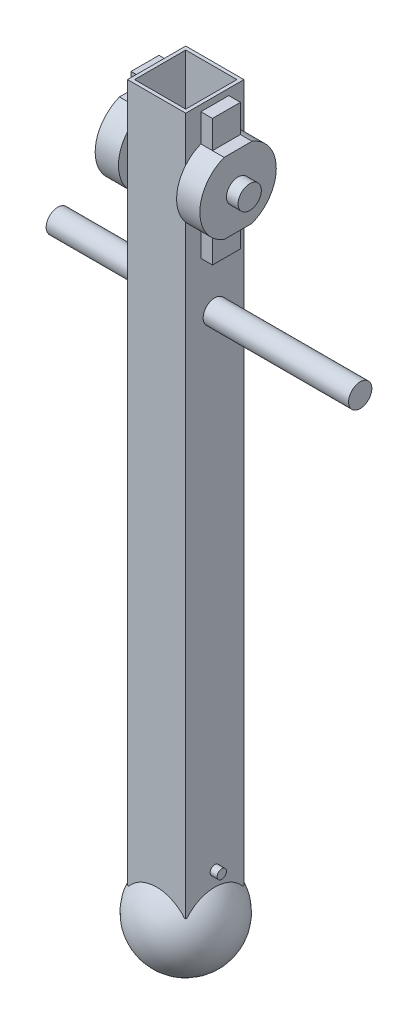
SolidWorks part; units mm, degrees
ref_plane "Front Plane" through (0, 0, 0) normal (0, 0, 1) x (1, 0, 0)
ref_plane "Top Plane" through (0, 0, 0) normal (0, 1, 0) x (1, 0, 0)
ref_plane "Right Plane" through (0, 0, 0) normal (1, 0, 0) x (0, 0, -1)
sketch "Sketch1" plane through (0, 0, 0) normal (0, 1, 0) x (1, 0, 0)
  line L0 (0, 56.0843) -> (0, -54.0393) construction
  line L1 (-85.0637, 0) -> (105.2276, 0) construction
  line L3 (-12.5, 12.5) -> (12.5, 12.5)
  line L4 (-12.5, 12.5) -> (-12.5, -12.5)
  line L5 (-12.5, -12.5) -> (12.5, -12.5)
  line L6 (12.5, 12.5) -> (12.5, -12.5)
  line L7 (-12.5, 12.5) -> (12.5, -12.5) construction
  line L8 (-12.5, -12.5) -> (12.5, 12.5) construction
  point P5 (0, 0)
  dimension "D1" = 25
  dimension "D2" = 25
extrude "Boss-Extrude1" add sketch "Sketch1" along normal blind 300
sketch "Sketch3" plane through (0, 0, 0) normal (0, -1, 0) x (1, 0, 0)
  line L0 (0, 13.6526) -> (0, -14.5281) construction
  line L1 (-18.6047, 0) -> (18.7142, 0) construction
  line L4 (-11, 11) -> (11, 11)
  line L5 (-11, 11) -> (-11, -11)
  line L6 (-11, -11) -> (11, -11)
  line L7 (11, 11) -> (11, -11)
  line L8 (-11, 11) -> (11, -11) construction
  line L9 (-11, -11) -> (11, 11) construction
  point P5 (0, 0)
  dimension "D1" = 22
  dimension "D2" = 22
extrude "Cut-Extrude1" cut sketch "Sketch3" against normal blind 300
ref_plane "Plane1" through (0, -10, 0) normal (0, -1, 0) x (-1, 0, 0)
sketch "Sketch4" plane through (0, -10, 0) normal (0, -1, 0) x (-1, 0, 0)
  line L0 (0, 13.2121) -> (0, -13.9344) construction
  line L1 (0, 20) -> (0, -20)
  arc A0 (0, 20) -> (0, -20) centre (0, 0) ccw
  dimension "D2" = 20
  dimension "D1" = 40
revolve "Revolve1" add sketch "Sketch4" angle 360 about L0
sketch "Sketch6" plane through (12.5, 0, 0) normal (1, 0, 0) x (0, 0, -1)
  line L0 (0, 22.0983) -> (0, -32.6766) construction
  line L1 (41.5847, -10) -> (-39.8607, -10) construction
  line L2 (-0.2807, -10) -> (0.2807, -10) construction
  circle A0 centre (0, 12) radius 2
  dimension "D2" = 4
  dimension "D1" = 22
extrude "Cut-Extrude3" cut sketch "Sketch6" against normal blind 25
sketch "Sketch9" plane through (-12.5, 0, 0) normal (-1, 0, 0) x (0, 0, 1)
  circle A0 centre (0, 12) radius 1.99
extrude "Boss-Extrude8" add sketch "Sketch9" against normal blind 28 separate body
sketch "Sketch10" plane through (-12.5, 0, 0) normal (-1, 0, 0) x (0, 0, 1)
  circle A0 centre (0, 12) radius 1.99
extrude "Boss-Extrude9" add sketch "Sketch10" along normal blind 3
sketch "Sketch11" plane through (12.5, 0, 0) normal (1, 0, 0) x (0, 0, -1)
  line L0 (0, 385.4895) -> (0, -90.331) construction
  line L1 (-12.5, 300) -> (12.5, 300) construction
  line L5 (-6, 285.2889) -> (-6, 297.2889)
  line L6 (6, 254.7111) -> (6, 242.7111)
  line L7 (6, 242.7111) -> (-6, 242.7111)
  line L8 (-6, 242.7111) -> (-6, 254.7111)
  line L9 (6, 285.2889) -> (6, 297.2889)
  line L10 (6, 297.2889) -> (-6, 297.2889)
  circle A1 centre (0, 270) radius 5
  circle A2 centre (0, 270) radius 16.4241
  arc A5 (-6, 254.7111) -> (6, 254.7111) centre (0, 270) ccw
  arc A6 (-6, 285.2889) -> (6, 285.2889) centre (0, 270) cw
  dimension "D1" = 12
  dimension "D2" = 30
  dimension "D3" = 6
  dimension "D8" = 12
  dimension "D4" = 6
  dimension "D5" = 6
  dimension "D6" = 6
  dimension "D7" = 12
extrude "Boss-Extrude10" add sketch "Sketch11" along normal blind 10 separate body contours A5 L0 L7 L6 | A1 L0 | L0 A1 | L0 A2 L8 L7 | A2 | L5 L10 L9 A6 region at (12.5, 270, -2.1221) region at (12.5, 270, 2.1221) region at (12.5, 248.3351, 3.0501) region at (12.5, 248.3351, -3.0501)
sketch "Sketch12" plane through (12.5, 0, 0) normal (1, 0, 0) x (0, 0, -1)
  line L3 (-12.5, 300) -> (12.5, 300) construction
  circle A5 centre (0, 270) radius 5
  circle A6 centre (0, 220) radius 5
  point P8 (0, 0)
  dimension "D1" = 80
extrude "Cut-Extrude4" cut sketch "Sketch12" against normal blind 1.5
sketch "Sketch15" plane through (22.5, 0, 0) normal (1, 0, 0) x (0, 0, -1)
  line L0 (-6, 254.7111) -> (-6, 242.7111)
  line L1 (-6, 242.7111) -> (6, 242.7111)
  line L2 (6, 242.7111) -> (6, 254.7111)
  line L3 (6, 254.7111) -> (-6, 254.7111)
  line L4 (-6, 285.2889) -> (6, 285.2889)
  line L5 (6, 285.2889) -> (6, 297.2889)
  line L6 (6, 285.2889) -> (6, 297.2889) construction
  line L7 (6, 297.2889) -> (-6, 297.2889)
  line L8 (-6, 285.2889) -> (-6, 297.2889) construction
  line L9 (6, 297.2889) -> (-6, 297.2889) construction
  line L10 (-6, 297.2889) -> (-6, 285.2889)
extrude "Cut-Extrude5" cut sketch "Sketch15" against normal blind 5
mirror "Mirror1" about plane through (0, 0, 0) normal (1, 0, 0) of "Cut-Extrude5", "Cut-Extrude4", "Boss-Extrude10"
sketch "Sketch13" plane through (0, 0, 0) normal (1, 0, 0) x (0, 0, -1)
  line L0 (-12.5, 300) -> (12.5, 300) construction
  circle A1 centre (0, 220) radius 5
  point P6 (-158.9402, 202.1097)
  dimension "D1" = 80
extrude "Boss-Extrude11" add sketch "Sketch13" along normal blind 75 and the other way blind 55
sketch "Sketch14" plane through (0, 0, 0) normal (1, 0, 0) x (0, 0, -1)
  circle A0 centre (0, 270) radius 5
extrude "Boss-Extrude12" add sketch "Sketch14" along normal blind 27.5 and the other way blind 22.5
